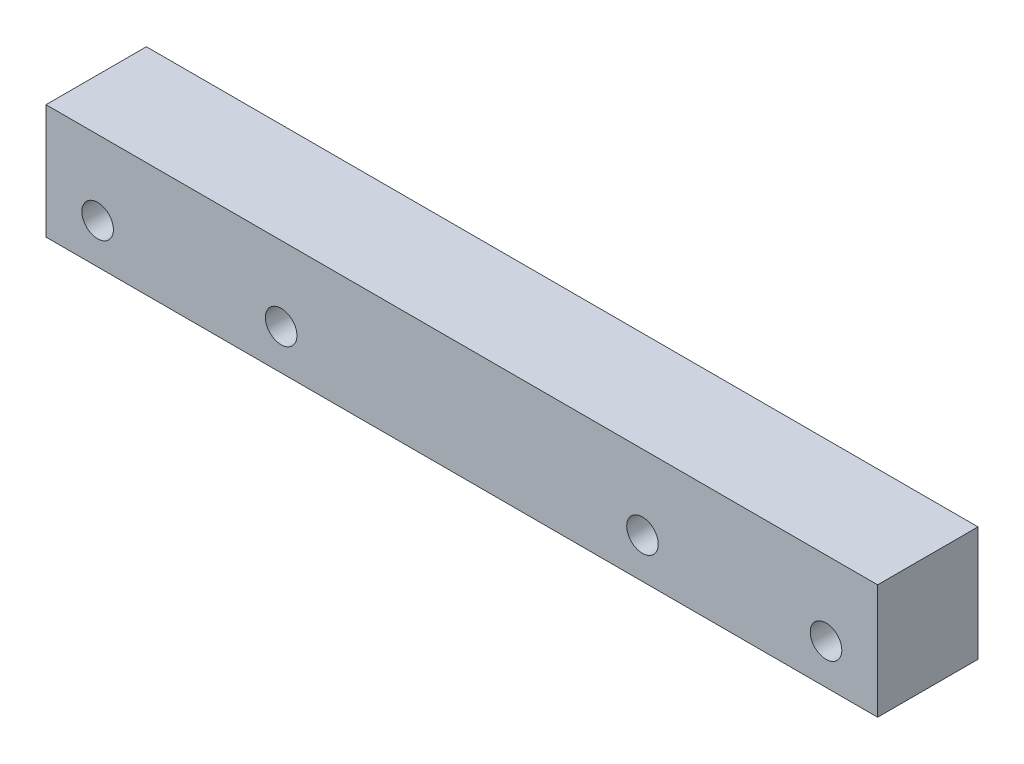
SolidWorks part; units mm, degrees
ref_plane "前视基准面" through (0, 0, 0) normal (0, 0, 1) x (1, 0, 0)
ref_plane "上视基准面" through (0, 0, 0) normal (0, 1, 0) x (1, 0, 0)
ref_plane "右视基准面" through (0, 0, 0) normal (1, 0, 0) x (0, 0, -1)
other "Configuration Table"
sketch "草图1" plane through (0, 0, 0) normal (0, 0, 1) x (1, 0, 0)
  line L1 (-72.5, -10) -> (72.5, -10)
  line L2 (-72.5, -10) -> (-72.5, 10)
  line L3 (-72.5, 10) -> (72.5, 10)
  line L4 (72.5, -10) -> (72.5, 10)
  line L5 (-72.5, -10) -> (72.5, 10) construction
  line L6 (-72.5, 10) -> (72.5, -10) construction
  point P0 (0, 0)
  dimension "D1" = 20
  dimension "D2" = 145
extrude "凸台-拉伸1" add sketch "草图1" along normal blind 17.5
sketch "草图2" plane through (0, 0, 0) normal (0, 0, -1) x (-1, 0, 0)
  line L0 (-72.5, -10) -> (-72.5, 10) construction
  line L1 (-72.5, 10) -> (72.5, 10) construction
  line L2 (0, 0) -> (0, -10) construction
  line L3 (72.5, -10) -> (-72.5, -10) construction
  circle A0 centre (-63.5, -3) radius 2.75
  circle A1 centre (-31.5, -3) radius 2.75
  circle A2 centre (31.5, -3) radius 2.75
  circle A3 centre (63.5, -3) radius 2.75
  dimension "D3" = 5.5
  dimension "D4" = 32
  dimension "D1" = 9
  dimension "D2" = 13
extrude "切除-拉伸1" cut sketch "草图2" against normal up to surface (17.5 mm away) up to face at (0, 0, 17.5)
